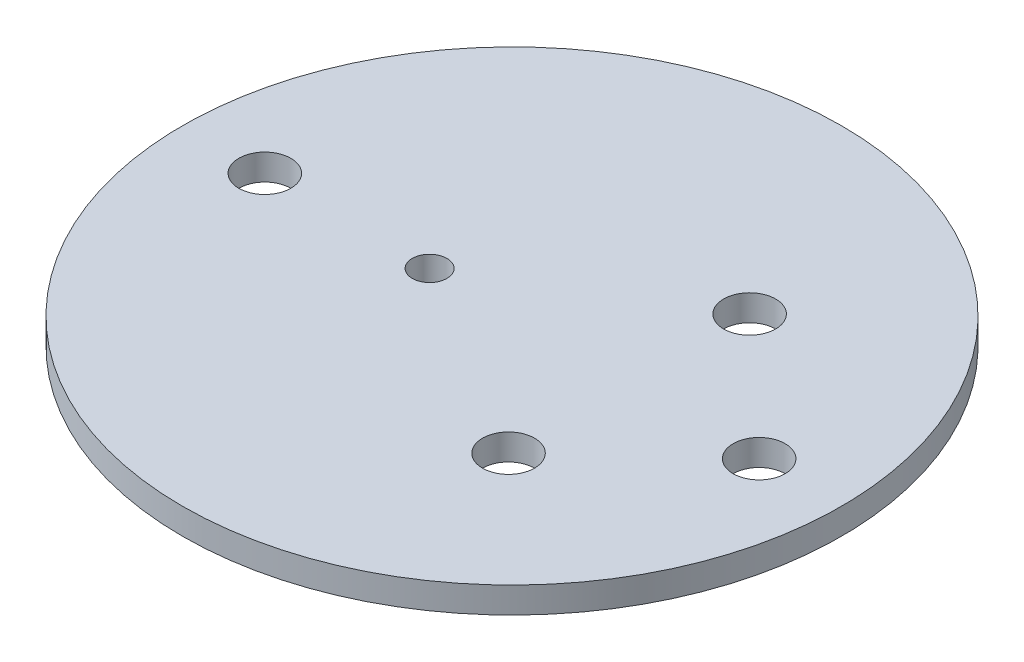
SolidWorks part; units mm, degrees
ref_plane "Front Plane" through (0, 0, 0) normal (0, 0, 1) x (1, 0, 0)
ref_plane "Top Plane" through (0, 0, 0) normal (0, 1, 0) x (1, 0, 0)
ref_plane "Right Plane" through (0, 0, 0) normal (1, 0, 0) x (0, 0, -1)
sketch "Sketch1" plane through (0, 0, 0) normal (0, 1, 0) x (1, 0, 0)
  line L0 (-28.5, 0) -> (28.5, 0) construction
  line L1 (13.5, 0) -> (13.5, 13.9)
  line L2 (13.5, 0) -> (13.5, -13.9)
  circle A1 centre (28.5, 0) radius 3
  circle A2 centre (-28.5, 0) radius 3
  circle A3 centre (13.5, 13.9) radius 3
  circle A4 centre (13.5, -13.9) radius 3
  circle A5 centre (-28.5, 0) radius 6.25 construction
  circle A6 centre (13.5, 13.9) radius 12.5 construction
  circle A7 centre (13.5, -13.9) radius 12.5 construction
  circle A8 centre (28.5, 0) radius 6.25 construction
  circle A9 centre (0, 0) radius 38
  circle A10 centre (-9.5, 0) radius 2
  circle A11 centre (-9.5, 0) radius 12.5 construction
  point P11 (0, 0)
  dimension "D1" = 76
  dimension "D3" = 6
  dimension "D4" = 13.9
  dimension "D5" = 6
  dimension "D6" = 12.5
  dimension "D7" = 25
  dimension "D8" = 4
  dimension "D9" = 25
  dimension "D2" = 57
  dimension "D10" = 9.5
  dimension "D11" = 13.5
extrude "Boss-Extrude1" add sketch "Sketch1" against normal blind 3 contours A4 A3 A2 A1 region at (-0.146, 0, 0)
